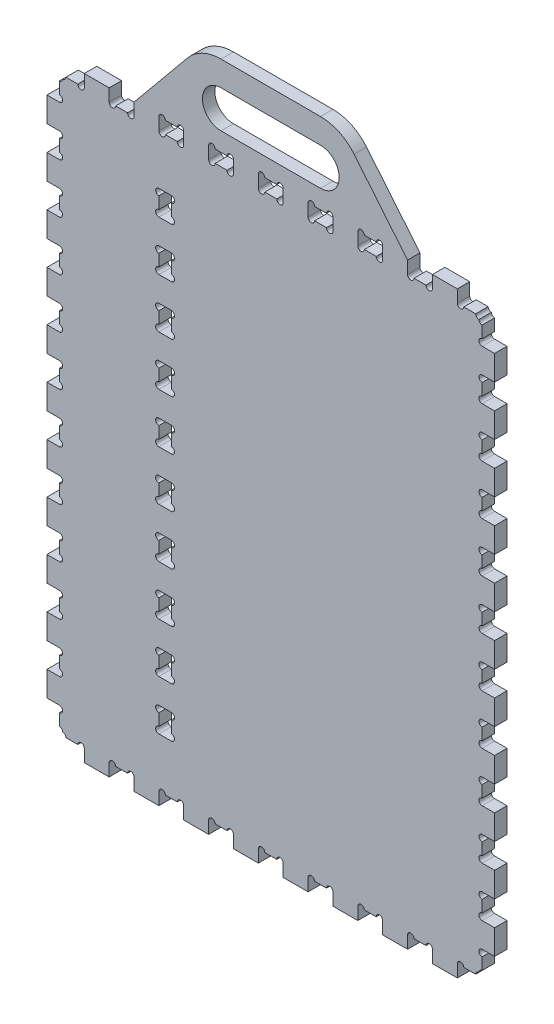
SolidWorks part; units mm, degrees
ref_plane "Front Plane" through (0, 0, 0) normal (0, 0, 1) x (1, 0, 0)
ref_plane "Top Plane" through (0, 0, 0) normal (0, 1, 0) x (1, 0, 0)
ref_plane "Right Plane" through (0, 0, 0) normal (1, 0, 0) x (0, 0, -1)
sketch "Sketch1" plane through (0, 0, 0) normal (0, 0, 1) x (1, 0, 0)
  line L1 (228.6, -304.8) -> (-228.6, -304.8)
  line L2 (228.6, -304.8) -> (228.6, 304.8)
  line L3 (228.6, 304.8) -> (-228.6, 304.8)
  line L4 (-228.6, -304.8) -> (-228.6, 304.8)
  line L5 (228.6, -304.8) -> (-228.6, 304.8) construction
  line L6 (228.6, 304.8) -> (-228.6, -304.8) construction
  line L9 (-203.2, 304.8) -> (-228.6, 304.8) construction
  point P0 (0, 0)
  dimension "D1" = 457.2
  dimension "D2" = 609.6
extrude "Boss-Extrude1" add sketch "Sketch1" along normal blind 12.7
sketch "Sketch2" plane through (0, 0, 12.7) normal (0, 0, 1) x (1, 0, 0)
  line L0 (228.6, 304.8) -> (-228.6, 304.8) construction
  line L1 (-215.9, 292.1) -> (-228.6, 292.1) construction
  line L2 (-215.9, 304.8) -> (-190.5, 304.8)
  line L3 (-215.9, 304.8) -> (-215.9, 292.1)
  line L4 (-215.9, 292.1) -> (-190.5, 292.1)
  line L5 (-190.5, 304.8) -> (-190.5, 292.1)
  line L6 (-228.6, 304.8) -> (-228.6, -304.8) construction
  circle A0 centre (-212.598, 292.1) radius 3.302
  circle A1 centre (-193.802, 292.1) radius 3.302
  line M10 (228.6, 304.8) -> (-228.6, 304.8)
  dimension "D4" = 6.604
  dimension "D5" = 6.604
  dimension "D1" = 25.4
  dimension "D2" = 12.7
  dimension "D3" = 12.7
extrude "Cut-Extrude1" cut sketch "Sketch2" against normal through all contours A1 L5 L3 A0 L4 M10 | L4 A0 | L4 A0 | L4 A1 | L4 A1 region at (-203.2, 299.0379, 12.7) region at (-212.598, 293.5014, 12.7) region at (-212.598, 290.6986, 12.7) region at (-193.802, 290.6986, 12.7) region at (-193.802, 293.5014, 12.7)
pattern_linear "LPattern1" count 9 spacing 50.8 along (1, 0, 0) of "Cut-Extrude1"
sketch "Sketch6" plane through (0, 0, 12.7) normal (0, 0, 1) x (1, 0, 0)
  line L1 (-228.6, 304.8) -> (-215.9, 304.8)
  line L2 (-228.6, 304.8) -> (-228.6, 292.1)
  line L3 (-228.6, 292.1) -> (-215.9, 292.1)
  line L4 (-215.9, 304.8) -> (-215.9, 292.1)
extrude "Cut-Extrude4" cut sketch "Sketch6" against normal through all
sketch "Sketch3" plane through (0, 0, 12.7) normal (0, 0, 1) x (1, 0, 0)
  line L0 (-228.6, 292.1) -> (-228.6, -304.8) construction
  line L1 (-228.6, 292.1) -> (-215.9, 292.1)
  line L2 (-228.6, 292.1) -> (-228.6, 266.7)
  line L3 (-228.6, 266.7) -> (-215.9, 266.7)
  line L4 (-215.9, 292.1) -> (-215.9, 266.7)
  line L5 (-215.9, 292.1) -> (-182.9158, 292.1) construction
  line L6 (-182.9158, 292.1) -> (-182.9158, 304.8) construction
  line L8 (-165.1, 304.8) -> (-190.5, 304.8) construction
  circle A0 centre (-215.9, 288.798) radius 3.302
  circle A1 centre (-215.9, 270.002) radius 3.302
  dimension "D3" = 6.604
  dimension "D4" = 6.604
  dimension "D1" = 25.4
  dimension "D2" = 12.7
  dimension "D5" = 12.7
extrude "Cut-Extrude2" cut sketch "Sketch3" against normal through all contours A1 L4 A0 L1 L2 L3 | L4 A0 | L4 A0 | L4 A1 | L4 A1 region at (-222.8379, 279.4, 12.7) region at (-214.4986, 288.798, 12.7) region at (-217.3014, 288.798, 12.7) region at (-217.3014, 270.002, 12.7) region at (-214.4986, 270.002, 12.7)
pattern_linear "LPattern2" count 12 spacing 50.8 along (0, -1, 0) of "Cut-Extrude2"
ref_plane "Plane1" through (0, 0, 0) normal (1, 0, 0) x (0, 0, -1)
ref_plane "Plane2" through (0, 0, 0) normal (0, 1, 0) x (1, 0, 0)
mirror "Mirror6" about plane through (0, 0, 0) normal (1, 0, 0) of "Cut-Extrude4"
mirror "Mirror7" about plane through (0, 0, 0) normal (0, 1, 0) of "Mirror6", "Cut-Extrude4"
mirror "Mirror1" about plane through (0, 0, 0) normal (1, 0, 0) of "LPattern2"
mirror "Mirror2" about plane through (0, 0, 0) normal (0, 1, 0) of "LPattern1"
sketch "Sketch9" plane through (0, 0, 12.7) normal (0, 0, 1) x (1, 0, 0)
  line L0 (-50.8, 342.9) -> (50.8, 342.9) construction
  line L1 (-50.8, 361.95) -> (50.8, 361.95)
  line L2 (-50.8, 323.85) -> (50.8, 323.85)
  line L3 (0, 342.9) -> (0, 292.1) construction
  line L4 (-6.096, 292.1) -> (6.096, 292.1) construction
  line L5 (-50.8, 387.35) -> (50.8, 387.35)
  line L7 (85.1274, 371.1389) -> (139.7, 304.8)
  line L8 (139.7, 304.8) -> (-139.7, 304.8)
  line L9 (-139.7, 304.8) -> (-85.1274, 371.1389)
  arc A0 (-50.8, 361.95) -> (-50.8, 323.85) centre (-50.8, 342.9) ccw
  arc A1 (50.8, 323.85) -> (50.8, 361.95) centre (50.8, 342.9) ccw
  arc A2 (-50.8, 387.35) -> (-85.1274, 371.1389) centre (-50.8, 342.9) ccw
  arc A3 (85.1274, 371.1389) -> (50.8, 387.35) centre (50.8, 342.9) ccw
  point P2 (0, 342.9)
  dimension "D1" = 38.1
  dimension "D2" = 101.6
  dimension "D3" = 38.1
  dimension "D4" = 25.4
extrude "Boss-Extrude3" add sketch "Sketch9" against normal blind 12.7
sketch "Sketch10" plane through (0, 0, 12.7) normal (0, 0, 1) x (1, 0, 0)
  line L0 (-114.3, 304.8) -> (-114.3, 292.1) construction
  line L1 (-114.3, 304.8) -> (-88.9, 304.8) construction
  line L2 (-88.9, 304.8) -> (-88.9, 292.1) construction
  circle A0 centre (-110.998, 304.8) radius 3.302
  circle A1 centre (-92.202, 304.8) radius 3.302
  point P4 (0, 0)
  point P9 (-93.0207, 304.8)
  dimension "D1" = 6.604
  dimension "D2" = 6.604
extrude "Cut-Extrude6" cut sketch "Sketch10" against normal blind 12.7
pattern_linear "LPattern3" count 5 spacing 50.8 along (1, 0, 0) of "Cut-Extrude6"
sketch "Sketch11" plane through (0, 0, 12.7) normal (0, 0, 1) x (1, 0, 0)
  line L0 (-114.3, 241.3) -> (-215.9, 241.3) construction
  line L1 (-114.3, 241.3) -> (-101.6, 241.3)
  line L2 (-114.3, 241.3) -> (-114.3, 215.9)
  line L3 (-114.3, 215.9) -> (-101.6, 215.9)
  line L4 (-101.6, 241.3) -> (-101.6, 215.9)
  circle A0 centre (-114.3, 237.998) radius 3.302
  circle A1 centre (-101.6, 237.998) radius 3.302
  circle A2 centre (-101.6, 219.202) radius 3.302
  circle A3 centre (-114.3, 219.202) radius 3.302
  arc A4 (-215.9, 234.696) -> (-215.9, 241.3) centre (-215.9, 237.998) ccw construction
  dimension "D3" = 6.604
  dimension "D1" = 12.7
  dimension "D2" = 25.4
  dimension "D4" = 101.6
extrude "Cut-Extrude7" cut sketch "Sketch11" against normal through all contours A3 L3 A2 L4 A1 L1 A0 L2 | L2 A0 | L2 A3 | L2 A3 | L4 A2 | L4 A2 | L4 A1 | L4 A1 | A0 region at (-107.95, 228.6, 12.7) region at (-115.7014, 237.998, 12.7) region at (-100.1986, 237.998, 12.7) region at (-103.0014, 237.998, 12.7) region at (-112.8986, 219.202, 12.7) region at (-115.7014, 219.202, 12.7) region at (-100.1986, 219.202, 12.7) region at (-103.0014, 219.202, 12.7)
pattern_linear "LPattern4" count 10 spacing 50.8 along (0, -1, 0) of "Cut-Extrude7"
